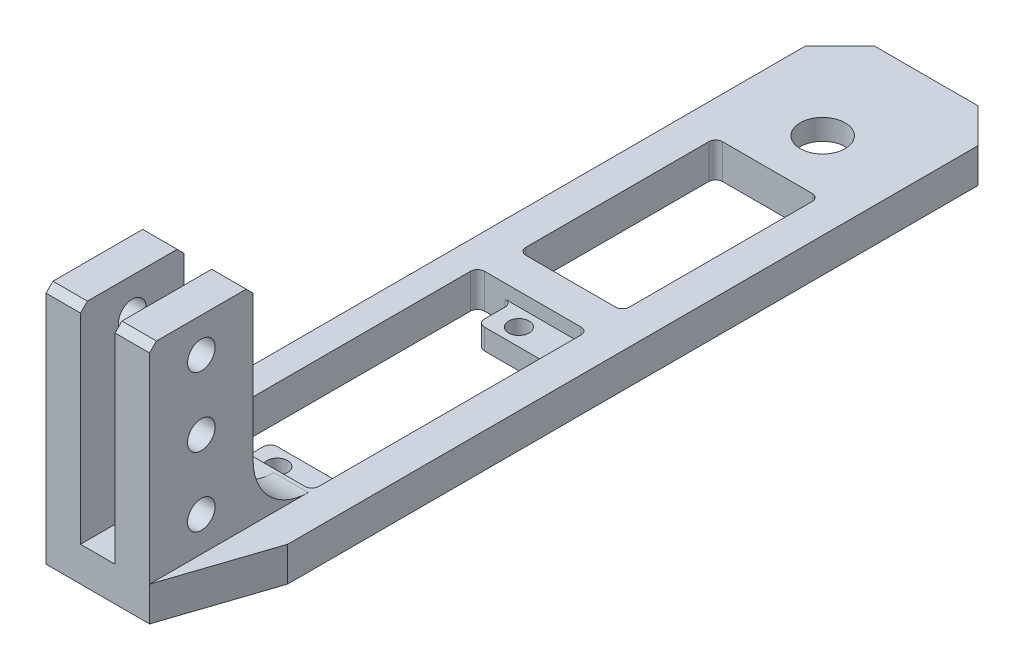
SolidWorks part; units mm, degrees
ref_plane "Front" through (0, 0, 0) normal (0, 0, 1) x (1, 0, 0)
ref_plane "Top" through (0, 0, 0) normal (0, 1, 0) x (1, 0, 0)
ref_plane "Right" through (0, 0, 0) normal (1, 0, 0) x (0, 0, -1)
sketch "Sketch1" plane through (0, 0, 0) normal (0, 1, 0) x (1, 0, 0)
  line L1 (-12.5, -60) -> (12.5, -60)
  line L2 (-12.5, -60) -> (-12.5, 60)
  line L3 (-12.5, 60) -> (12.5, 60)
  line L4 (12.5, -60) -> (12.5, 60)
  line L5 (-12.5, -60) -> (12.5, 60) construction
  line L6 (-12.5, 60) -> (12.5, -60) construction
  point P0 (0, 0)
  dimension "D1" = 120
  dimension "D2" = 25
extrude "Boss-Extrude1" add sketch "Sketch1" along normal blind 5
sketch "Sketch2" plane through (0, 5, 0) normal (0, 1, 0) x (1, 0, 0)
  line L0 (-12.5, -60) -> (12.5, -60) construction
  line L1 (-7.5, -60) -> (7.5, -60)
  line L2 (-7.5, -60) -> (-7.5, -45)
  line L3 (-7.5, -45) -> (7.5, -45)
  line L4 (7.5, -60) -> (7.5, -45)
  line L5 (0, 0) -> (0, -7.7795) construction
  line L7 (-2.5, -45) -> (2.5, -45)
  line L8 (-2.5, -45) -> (-2.5, -60)
  line L9 (-2.5, -60) -> (2.5, -60)
  line L10 (2.5, -45) -> (2.5, -60)
  line M9 (-12.5, -60) -> (12.5, -60)
  dimension "D1" = 15
  dimension "D2" = 15
  dimension "D3" = 5
extrude "Boss-Extrude2" add sketch "Sketch2" along normal blind 30 contours L8 L3 L2 M9 | L3 L10 L4 M9 region at (-5, 5, 52.5) region at (5, 5, 52.5)
chamfer "Chamfer1" distance 5 distance2 15 1 edges at (12.5, 2.5, 60) first distance on face at (0, 14.1667, 60)
chamfer "Chamfer2" distance 15 distance2 5 1 edges at (-12.5, 2.5, 60) first distance on face at (-12.5, 2.5, 0)
chamfer "Chamfer3" distance 1 angle 45 4 edges at (5, 35, 60) (-5, 35, 60) (-5, 35, 45) (5, 35, 45)
chamfer "Chamfer4" distance 5 angle 45 2 edges at (-12.5, 2.5, -60) (12.5, 2.5, -60)
sketch "Sketch5" plane through (0, 5, 0) normal (0, 1, 0) x (1, 0, 0)
  line L0 (-2.5, -60) -> (2.5, -60) construction
  line L1 (7.5, 60) -> (-7.5, 60) construction
  circle A0 centre (0, -7.5) radius 5 construction
  circle A1 centre (0, 45) radius 5 construction
  dimension "D2" = 10
  dimension "D4" = 10
  dimension "D1" = 52.5
  dimension "D3" = 15
sketch "Sketch3" plane through (0, 5, 0) normal (0, 1, 0) x (1, 0, 0)
  line L0 (0, 0) -> (0, 25.0391) construction
  line L1 (-8.5, -36.5) -> (7.5, -36.5)
  line L2 (-8.5, -36.5) -> (-8.5, 3.5)
  line L3 (-8.5, 3.5) -> (7.5, 3.5)
  line L4 (7.5, -36.5) -> (7.5, 3.5)
  line L5 (-8.5, -36.5) -> (7.5, 3.5) construction
  line L6 (-8.5, 3.5) -> (7.5, -36.5) construction
  line L7 (-0.5, -16.5) -> (-22.7755, -16.5) construction
  line L8 (-3.5, 3.5) -> (7.5, 3.5)
  line L9 (-3.5, 3.5) -> (-3.5, -1.5)
  line L10 (-3.5, -1.5) -> (7.5, -1.5)
  line L11 (7.5, 3.5) -> (7.5, -1.5)
  line L12 (-3.5, -36.5) -> (7.5, -36.5)
  line L13 (-3.5, -36.5) -> (-3.5, -31.5)
  line L14 (-3.5, -31.5) -> (7.5, -31.5)
  line L15 (7.5, -36.5) -> (7.5, -31.5)
  line L16 (12.5, -45) -> (12.5, 55) construction
  point P0 (-0.5, -16.5)
  point P18 (-21.8577, -16.5)
  point P19 (-7.5822, 3.5)
  point P23 (-2.8944, -1.5)
  dimension "D1" = 16
  dimension "D2" = 40
  dimension "D3" = 11
  dimension "D4" = 5
  dimension "D5" = 11
  dimension "D7" = 5
extrude "Cut-Extrude1" cut sketch "Sketch3" against normal through all contours L15 L1 L4 L3 L11 L10 L9 L2 L13 L14 region at (-1.0189, 5, 16.5)
extrude "Cut-Extrude2" cut sketch "Sketch3<3>" against normal blind 2 contours L11 L3 L9 L10 | L1 L15 L14 L13 region at (2, 5, 34) region at (2, 5, -1)
sketch "Sketch3<3>" plane through (0, 5, 0) normal (0, 1, 0) x (1, 0, 0) same geometry as "Sketch3"
fillet "Fillet1" radius 1 8 edges at (7.5, 4, 36.5) (-3.5, 1.5, 31.5) (-3.5, 1.5, 36.5) (-8.5, 2.5, 36.5) (-3.5, 1.5, 1.5) (-3.5, 1.5, -3.5) (7.5, 4, -3.5) (-8.5, 2.5, -3.5)
sketch "Sketch4" plane through (0, 3, 0) normal (0, 1, 0) x (1, 0, 0)
  line L0 (0, 3.5) -> (0, -28.1892) construction
  line L1 (-4.5, 3.5) -> (6.5, 3.5) construction
  circle A0 centre (0, 1) radius 1.5
  circle A1 centre (0, -34) radius 1.5
  point P8 (1.5, -16.5)
  point P9 (0, 0)
  dimension "D2" = 3
  dimension "D1" = 35
  dimension "D3" = 2.5
extrude "Cut-Extrude3" cut sketch "Sketch4" against normal through all
fillet "Fillet2" radius 8 2 edges at (-5, 5, 45) (5, 5, 45)
sketch "Sketch6" plane through (0, 5, 0) normal (0, 1, 0) x (1, 0, 0)
  circle A0 centre (0, 45) radius 3.25
  dimension "D1" = 6.5
extrude "Cut-Extrude5" cut sketch "Sketch6" against normal through all
sketch "Sketch7" plane through (0, 0, 0) normal (0, -1, 0) x (1, 0, 0)
  line L0 (-6.6849, -39.75) -> (6.6849, -39.75)
  line L1 (-6.6849, -50.25) -> (6.6849, -50.25)
  line L2 (0, -45) -> (-19.1578, -45) construction
  circle A0 centre (0, -45) radius 8.5 construction
  arc A1 (-6.6849, -39.75) -> (-6.6849, -50.25) centre (0, -45) ccw
  arc A2 (6.6849, -39.75) -> (6.6849, -50.25) centre (0, -45) cw
  dimension "D1" = 17
  dimension "D2" = 10.5
extrude "Cut-Extrude6" cut sketch "Sketch7" against normal blind 2
sketch "Sketch8" plane through (0, 2, 0) normal (0, -1, 0) x (1, 0, 0)
  line L0 (0, -45) -> (-2.0583, -45) construction
  line L1 (-8.5, -43.75) -> (-6.5, -43.75)
  line L2 (-8.5, -43.75) -> (-8.5, -46.25)
  line L3 (-8.5, -46.25) -> (-6.5, -46.25)
  line L4 (-6.5, -43.75) -> (-6.5, -46.25)
  arc A0 (-6.6849, -39.75) -> (-6.6849, -50.25) centre (0, -45) ccw construction
  dimension "D1" = 2.5
  dimension "D2" = 2
extrude "Cut-Extrude7" cut sketch "Sketch8" against normal blind 1
sketch "Sketch9" plane through (7.5, 0, 0) normal (1, 0, 0) x (0, 0, -1)
  line L1 (-52.5, 35) -> (-52.5, 41.8125) construction
  line L2 (-59, 35) -> (-46, 35) construction
  circle A0 centre (-52.5, 30) radius 2
  circle A1 centre (-52.5, 20) radius 2
  circle A2 centre (-52.5, 10) radius 2
  dimension "D3" = 4
  dimension "D1" = 10
  dimension "D2" = 10
  dimension "D4" = 5
extrude "Cut-Extrude8" cut sketch "Sketch9" against normal through all
sketch "Sketch10" plane through (0, 5, 0) normal (0, 1, 0) x (1, 0, 0)
  line L0 (-7.5, 3.5) -> (6.5, 3.5) construction
  line L1 (-7.5, 37) -> (7.5, 37)
  line L2 (-7.5, 37) -> (-7.5, 8.5)
  line L3 (-7.5, 8.5) -> (7.5, 8.5)
  line L4 (7.5, 37) -> (7.5, 8.5)
  line L7 (-12.5, 55) -> (-12.5, -45) construction
  line L8 (12.5, -45) -> (12.5, 55) construction
  dimension "D1" = 8
  dimension "D2" = 5
  dimension "D3" = 5
  dimension "D4" = 5
extrude "Cut-Extrude9" cut sketch "Sketch10" against normal through all
fillet "Fillet3" radius 1 4 edges at (-7.5, 2.5, -8.5) (7.5, 2.5, -8.5) (7.5, 2.5, -37) (-7.5, 2.5, -37)
